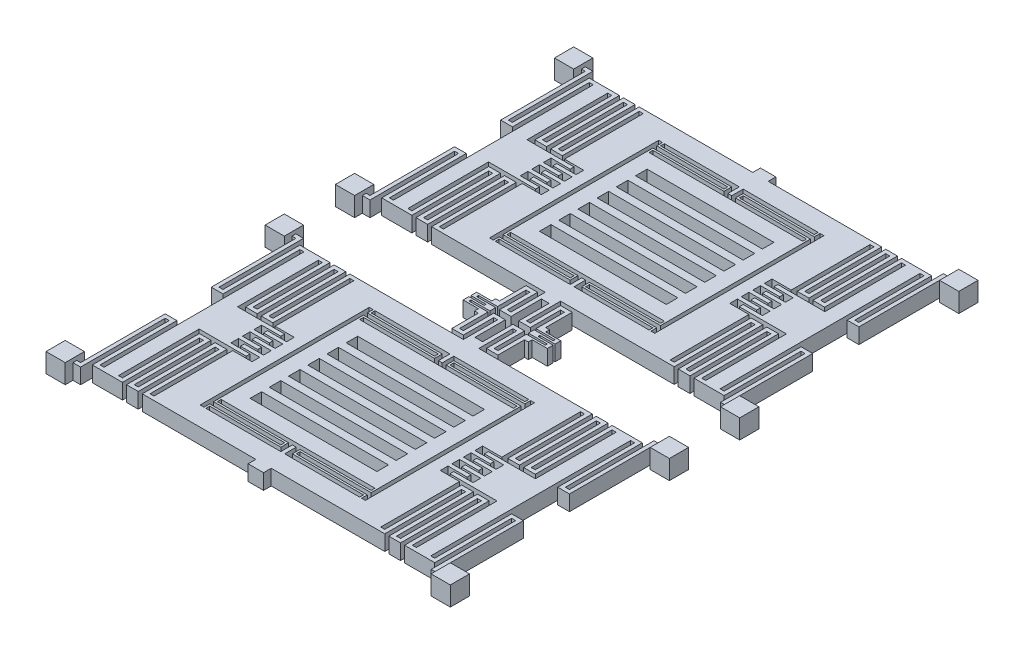
SolidWorks part; units mm, degrees
ref_plane "Front Plane" through (0, 0, 0) normal (0, 0, 1) x (1, 0, 0)
ref_plane "Top Plane" through (0, 0, 0) normal (0, 1, 0) x (1, 0, 0)
ref_plane "Right Plane" through (0, 0, 0) normal (1, 0, 0) x (0, 0, -1)
sketch "Sketch1" plane through (0, 0, 0) normal (0, 1, 0) x (1, 0, 0)
  line L0 (-0.165, 0.06) -> (-0.165, 0.09)
  line L1 (-0.205, -0.18) -> (0.205, -0.18)
  line L2 (-0.205, -0.18) -> (-0.205, 0.18)
  line L3 (-0.205, 0.18) -> (0.205, 0.18)
  line L4 (0.205, -0.18) -> (0.205, 0.18)
  line L5 (0, 0.18) -> (0, -0.18) construction
  line L6 (-0.205, 0) -> (0.205, 0) construction
  line L7 (0.165, 0.01) -> (-0.165, 0.01)
  line L8 (0.165, 0.01) -> (0.165, 0.04)
  line L9 (0.165, 0.04) -> (-0.165, 0.04)
  line L10 (-0.165, 0.01) -> (-0.165, 0.04)
  line L11 (0, 0.04) -> (0, 0.01) construction
  line L12 (0.165, 0.025) -> (-0.165, 0.025) construction
  line L13 (0.165, 0.09) -> (-0.165, 0.09)
  line L14 (0.165, 0.06) -> (-0.165, 0.06)
  line L15 (0.165, 0.06) -> (0.165, 0.09)
  line L16 (-0.165, 0.11) -> (-0.165, 0.14)
  line L17 (0.165, 0.14) -> (-0.165, 0.14)
  line L18 (0.165, 0.11) -> (-0.165, 0.11)
  line L19 (0.165, 0.11) -> (0.165, 0.14)
  line L20 (-0.165, 0.01) -> (-0.165, 0.06) construction
  line L21 (0.165, -0.11) -> (-0.165, -0.11)
  line L22 (0.165, -0.11) -> (0.165, -0.14)
  line L23 (0.165, -0.14) -> (-0.165, -0.14)
  line L24 (-0.165, -0.11) -> (-0.165, -0.14)
  line L25 (0.165, -0.06) -> (-0.165, -0.06)
  line L26 (0.165, -0.06) -> (0.165, -0.09)
  line L27 (0.165, -0.09) -> (-0.165, -0.09)
  line L28 (-0.165, -0.06) -> (-0.165, -0.09)
  line L29 (0.165, -0.04) -> (-0.165, -0.04)
  line L30 (-0.165, -0.01) -> (-0.165, -0.04)
  line L31 (0.165, -0.01) -> (-0.165, -0.01)
  line L32 (0.165, -0.01) -> (0.165, -0.04)
  point P0 (0, 0)
  point P4 (0, 0.025)
  dimension "D1" = 0.36
  dimension "D2" = 0.41
  dimension "D3" = 0.33
  dimension "D4" = 0.03
  dimension "D5" = 0.01
  dimension "D7" = 0.05
  dimension "D6" = 3
extrude "Boss-Extrude1" add sketch "Sketch1" along normal blind 0.04
sketch "Sketch2" plane through (0, 0, 0) normal (0, 1, 0) x (1, 0, 0)
  line L0 (0.2254, 0) -> (-0.371, 0) construction
  line L5 (0, 0) -> (0, 0.338) construction
  line L7 (-0.215, -0.22) -> (-0.215, 0.22)
  line L13 (-0.295, 0.27) -> (-0.02, 0.27)
  line L15 (-0.005, 0.22) -> (-0.2, 0.22)
  line L16 (-0.205, 0.18) -> (-0.205, -0.18) construction
  line L18 (0.005, 0.19) -> (-0.005, 0.19)
  line L19 (-0.005, 0.19) -> (-0.005, 0.22)
  line L20 (-0.205, 0.18) -> (-0.205, 0.195)
  line L21 (-0.205, 0.195) -> (-0.02, 0.195)
  line L22 (-0.02, 0.195) -> (-0.02, 0.205)
  line L23 (-0.02, 0.205) -> (-0.205, 0.205)
  line L24 (-0.205, 0.205) -> (-0.205, 0.22)
  line L26 (-0.2, 0.22) -> (-0.2, 0.21)
  line L27 (-0.2, 0.21) -> (-0.015, 0.21)
  line L28 (-0.015, 0.21) -> (-0.015, 0.19)
  line L29 (-0.015, 0.19) -> (-0.2, 0.19)
  line L30 (-0.2, 0.19) -> (-0.2, 0.18)
  line L31 (0.205, 0.18) -> (-0.205, 0.18) construction
  line L32 (-0.2, 0.18) -> (-0.205, 0.18)
  line L33 (-0.205, 0.22) -> (-0.215, 0.22)
  line L34 (-0.295, -0.005) -> (-0.295, 0.005)
  line L35 (-0.295, 0.005) -> (-0.245, 0.005)
  line L36 (-0.245, 0.005) -> (-0.245, 0.025)
  line L37 (-0.245, 0.055) -> (-0.295, 0.055)
  line L38 (-0.295, 0.055) -> (-0.295, 0.27)
  line L39 (-0.245, 0.035) -> (-0.295, 0.035)
  line L40 (-0.295, 0.035) -> (-0.295, 0.025)
  line L41 (-0.295, 0.025) -> (-0.245, 0.025)
  line L42 (-0.245, 0.035) -> (-0.245, 0.055)
  line L43 (0.295, -0.005) -> (0.295, 0.005)
  line L45 (0.215, -0.22) -> (0.215, 0.22)
  line L46 (0.205, 0.22) -> (0.215, 0.22)
  line L47 (0.205, 0.205) -> (0.205, 0.22)
  line L48 (0.02, 0.205) -> (0.205, 0.205)
  line L49 (0.02, 0.195) -> (0.02, 0.205)
  line L50 (0.205, 0.195) -> (0.02, 0.195)
  line L51 (0.205, 0.18) -> (0.205, 0.195)
  line L52 (0.2, 0.18) -> (0.205, 0.18)
  line L53 (0.2, 0.19) -> (0.2, 0.18)
  line L54 (0.015, 0.19) -> (0.2, 0.19)
  line L55 (0.015, 0.21) -> (0.015, 0.19)
  line L56 (0.2, 0.21) -> (0.015, 0.21)
  line L57 (0.2, 0.22) -> (0.2, 0.21)
  line L58 (0.005, 0.22) -> (0.2, 0.22)
  line L59 (0.005, 0.19) -> (0.005, 0.22)
  line L60 (0.295, 0.055) -> (0.295, 0.27)
  line L61 (0.245, 0.055) -> (0.295, 0.055)
  line L62 (0.245, 0.035) -> (0.245, 0.055)
  line L63 (0.245, 0.035) -> (0.295, 0.035)
  line L64 (0.295, 0.035) -> (0.295, 0.025)
  line L65 (0.295, 0.025) -> (0.245, 0.025)
  line L66 (0.245, 0.005) -> (0.245, 0.025)
  line L67 (0.295, 0.005) -> (0.245, 0.005)
  line L68 (0.205, -0.22) -> (0.215, -0.22)
  line L69 (0.205, -0.205) -> (0.205, -0.22)
  line L70 (0.02, -0.205) -> (0.205, -0.205)
  line L71 (0.02, -0.195) -> (0.02, -0.205)
  line L72 (0.205, -0.195) -> (0.02, -0.195)
  line L73 (0.205, -0.18) -> (0.205, -0.195)
  line L74 (0.2, -0.18) -> (0.205, -0.18)
  line L75 (0.2, -0.19) -> (0.2, -0.18)
  line L76 (0.015, -0.19) -> (0.2, -0.19)
  line L77 (0.015, -0.21) -> (0.015, -0.19)
  line L78 (0.2, -0.21) -> (0.015, -0.21)
  line L79 (0.2, -0.22) -> (0.2, -0.21)
  line L80 (0.005, -0.22) -> (0.2, -0.22)
  line L81 (0.005, -0.19) -> (0.005, -0.22)
  line L82 (0.005, -0.19) -> (-0.005, -0.19)
  line L83 (-0.005, -0.19) -> (-0.005, -0.22)
  line L84 (-0.005, -0.22) -> (-0.2, -0.22)
  line L85 (-0.2, -0.22) -> (-0.2, -0.21)
  line L86 (-0.2, -0.21) -> (-0.015, -0.21)
  line L87 (-0.015, -0.21) -> (-0.015, -0.19)
  line L88 (-0.015, -0.19) -> (-0.2, -0.19)
  line L89 (-0.2, -0.19) -> (-0.2, -0.18)
  line L90 (-0.2, -0.18) -> (-0.205, -0.18)
  line L91 (-0.205, -0.18) -> (-0.205, -0.195)
  line L92 (-0.205, -0.195) -> (-0.02, -0.195)
  line L93 (-0.02, -0.195) -> (-0.02, -0.205)
  line L94 (-0.02, -0.205) -> (-0.205, -0.205)
  line L95 (-0.205, -0.205) -> (-0.205, -0.22)
  line L96 (-0.205, -0.22) -> (-0.215, -0.22)
  line L97 (-0.295, -0.005) -> (-0.245, -0.005)
  line L98 (-0.245, -0.005) -> (-0.245, -0.025)
  line L99 (-0.295, -0.025) -> (-0.245, -0.025)
  line L100 (-0.295, -0.035) -> (-0.295, -0.025)
  line L101 (-0.245, -0.035) -> (-0.295, -0.035)
  line L102 (-0.245, -0.035) -> (-0.245, -0.055)
  line L103 (-0.245, -0.055) -> (-0.295, -0.055)
  line L104 (-0.295, -0.055) -> (-0.295, -0.27)
  line L105 (-0.295, -0.27) -> (-0.02, -0.27)
  line L106 (0.295, -0.055) -> (0.295, -0.27)
  line L107 (0.245, -0.055) -> (0.295, -0.055)
  line L108 (0.245, -0.035) -> (0.245, -0.055)
  line L109 (0.245, -0.035) -> (0.295, -0.035)
  line L110 (0.295, -0.035) -> (0.295, -0.025)
  line L111 (0.295, -0.025) -> (0.245, -0.025)
  line L112 (0.245, -0.005) -> (0.245, -0.025)
  line L113 (0.295, -0.005) -> (0.245, -0.005)
  line L114 (0.02, 0.27) -> (0.295, 0.27)
  line L116 (-0.02, 0.27) -> (-0.02, 0.29)
  line L117 (-0.02, 0.29) -> (0.02, 0.29)
  line L118 (0.02, 0.27) -> (0.02, 0.29)
  line L119 (0, 0.29) -> (0, 0.27) construction
  line L120 (-0.02, 0.28) -> (0.02, 0.28) construction
  line L121 (0.02, -0.27) -> (0.02, -0.29)
  line L122 (-0.02, -0.29) -> (0.02, -0.29)
  line L123 (-0.02, -0.27) -> (-0.02, -0.29)
  line L124 (0.02, -0.27) -> (0.295, -0.27)
  point P2 (-0.21, -0.22)
  point P759 (0, 0.28)
  dimension "D2" = 0.01
  dimension "D3" = 0.01
  dimension "D4" = 0.54
  dimension "D5" = 0.03
  dimension "D6" = 0.59
  dimension "D7" = 0.015
  dimension "D8" = 0.005
  dimension "D10" = 0.01
  dimension "D11" = 0.02
  dimension "D12" = 0.185
  dimension "D13" = 0.005
  dimension "D14" = 0.005
  dimension "D15" = 0.005
  dimension "D16" = 0.05
  dimension "D17" = 0.11
  dimension "D18" = 0.01
  dimension "D19" = 0.44
  dimension "D20" = 0.04
extrude "Boss-Extrude2" add sketch "Sketch2" along normal blind 0.04
sketch "Sketch3" plane through (0, 0, 0) normal (0, 1, 0) x (1, 0, 0)
  line L1 (-0.315, 0.01) -> (-0.265, 0.01)
  line L2 (-0.265, 0.01) -> (-0.265, 0.02)
  line L3 (-0.265, 0.02) -> (-0.315, 0.02)
  line L4 (-0.315, 0.02) -> (-0.315, 0.04)
  line L5 (-0.315, 0.04) -> (-0.265, 0.04)
  line L6 (-0.265, 0.04) -> (-0.265, 0.05)
  line L7 (-0.265, 0.05) -> (-0.315, 0.05)
  line L8 (-0.315, 0.05) -> (-0.3875, 0.05)
  line L11 (0, 0) -> (-0.4867, 0) construction
  line L12 (-0.295, 0.035) -> (-0.295, 0.025) construction
  line L14 (0, 0) -> (0, 0.4313) construction
  line L20 (-0.3875, 0.27) -> (-0.367, 0.27)
  line L21 (-0.367, 0.27) -> (-0.367, 0.07)
  line L22 (-0.367, 0.07) -> (-0.3565, 0.07)
  line L23 (-0.3565, 0.07) -> (-0.3565, 0.27)
  line L24 (-0.3565, 0.27) -> (-0.326, 0.27)
  line L25 (-0.326, 0.27) -> (-0.326, 0.07)
  line L26 (-0.326, 0.07) -> (-0.3155, 0.07)
  line L27 (-0.3155, 0.07) -> (-0.3155, 0.27)
  line L28 (-0.3155, 0.27) -> (-0.295, 0.27)
  line L30 (-0.3875, 0.26) -> (-0.377, 0.26)
  line L31 (-0.377, 0.26) -> (-0.377, 0.06)
  line L32 (-0.377, 0.06) -> (-0.3465, 0.06)
  line L33 (-0.3465, 0.06) -> (-0.3465, 0.26)
  line L34 (-0.3465, 0.26) -> (-0.336, 0.26)
  line L35 (-0.336, 0.26) -> (-0.336, 0.06)
  line L36 (-0.336, 0.06) -> (-0.3055, 0.06)
  line L37 (-0.3055, 0.06) -> (-0.3055, 0.26)
  line L38 (-0.3055, 0.26) -> (-0.295, 0.26)
  line L39 (-0.295, 0.27) -> (-0.295, 0.055) construction
  line L40 (-0.295, 0.27) -> (-0.295, 0.26)
  line L41 (-0.3875, 0.26) -> (-0.3875, 0.05)
  line L136 (-0.425, 0.05) -> (-0.425, -0.05)
  line L138 (-0.315, -0.01) -> (-0.315, 0.01)
  line L139 (-0.3875, 0.27) -> (-0.425, 0.27)
  line L140 (-0.425, 0.05) -> (-0.425, 0.26)
  line L141 (-0.4063, 0.27) -> (-0.4063, -0.0104) construction
  line L142 (-0.456, 0.27) -> (-0.456, 0.29)
  line L143 (-0.456, 0.29) -> (-0.476, 0.29)
  line L144 (-0.476, 0.29) -> (-0.476, 0.28)
  line L145 (-0.476, 0.28) -> (-0.466, 0.28)
  line L146 (-0.466, 0.28) -> (-0.466, 0.26)
  line L147 (-0.425, -0.05) -> (-0.425, -0.26)
  line L148 (-0.425, -0.26) -> (-0.4355, -0.26)
  line L149 (-0.4355, -0.26) -> (-0.4355, -0.06)
  line L150 (-0.4355, -0.06) -> (-0.466, -0.06)
  line L151 (-0.466, -0.06) -> (-0.466, -0.26)
  line L152 (-0.456, 0.07) -> (-0.456, 0.27)
  line L153 (-0.466, 0.06) -> (-0.466, 0.26)
  line L154 (-0.4455, 0.07) -> (-0.456, 0.07)
  line L155 (-0.4355, 0.06) -> (-0.466, 0.06)
  line L156 (-0.4455, 0.27) -> (-0.4455, 0.07)
  line L157 (-0.4355, 0.26) -> (-0.4355, 0.06)
  line L158 (-0.425, 0.27) -> (-0.4455, 0.27)
  line L159 (-0.425, 0.26) -> (-0.4355, 0.26)
  line L160 (-0.466, -0.28) -> (-0.466, -0.26)
  line L161 (-0.476, -0.28) -> (-0.466, -0.28)
  line L162 (-0.476, -0.29) -> (-0.476, -0.28)
  line L163 (-0.456, -0.29) -> (-0.476, -0.29)
  line L164 (-0.456, -0.27) -> (-0.456, -0.29)
  line L165 (-0.456, -0.07) -> (-0.456, -0.27)
  line L166 (-0.4455, -0.07) -> (-0.456, -0.07)
  line L167 (-0.4455, -0.27) -> (-0.4455, -0.07)
  line L168 (-0.425, -0.27) -> (-0.4455, -0.27)
  line L169 (-0.3875, -0.27) -> (-0.425, -0.27)
  line L170 (-0.3875, -0.27) -> (-0.367, -0.27)
  line L171 (-0.367, -0.27) -> (-0.367, -0.07)
  line L172 (-0.367, -0.07) -> (-0.3565, -0.07)
  line L173 (-0.3565, -0.07) -> (-0.3565, -0.27)
  line L174 (-0.3565, -0.27) -> (-0.326, -0.27)
  line L175 (-0.326, -0.27) -> (-0.326, -0.07)
  line L176 (-0.326, -0.07) -> (-0.3155, -0.07)
  line L177 (-0.3155, -0.07) -> (-0.3155, -0.27)
  line L178 (-0.3155, -0.27) -> (-0.295, -0.27)
  line L179 (-0.295, -0.27) -> (-0.295, -0.26)
  line L180 (-0.3055, -0.26) -> (-0.295, -0.26)
  line L181 (-0.3055, -0.06) -> (-0.3055, -0.26)
  line L182 (-0.336, -0.06) -> (-0.3055, -0.06)
  line L183 (-0.336, -0.26) -> (-0.336, -0.06)
  line L184 (-0.3465, -0.26) -> (-0.336, -0.26)
  line L185 (-0.3465, -0.06) -> (-0.3465, -0.26)
  line L186 (-0.377, -0.06) -> (-0.3465, -0.06)
  line L187 (-0.377, -0.26) -> (-0.377, -0.06)
  line L188 (-0.3875, -0.26) -> (-0.377, -0.26)
  line L189 (-0.3875, -0.26) -> (-0.3875, -0.05)
  line L190 (-0.315, -0.05) -> (-0.3875, -0.05)
  line L191 (-0.265, -0.05) -> (-0.315, -0.05)
  line L192 (-0.265, -0.04) -> (-0.265, -0.05)
  line L193 (-0.315, -0.04) -> (-0.265, -0.04)
  line L194 (-0.315, -0.02) -> (-0.315, -0.04)
  line L195 (-0.265, -0.02) -> (-0.315, -0.02)
  line L196 (-0.265, -0.01) -> (-0.265, -0.02)
  line L197 (-0.315, -0.01) -> (-0.265, -0.01)
  line L198 (0.425, 0.05) -> (0.425, -0.05)
  line L199 (0.425, 0.05) -> (0.425, 0.26)
  line L200 (0.425, 0.26) -> (0.4355, 0.26)
  line L201 (0.4355, 0.26) -> (0.4355, 0.06)
  line L202 (0.4355, 0.06) -> (0.466, 0.06)
  line L203 (0.466, 0.06) -> (0.466, 0.26)
  line L204 (0.466, 0.28) -> (0.466, 0.26)
  line L205 (0.476, 0.28) -> (0.466, 0.28)
  line L206 (0.476, 0.29) -> (0.476, 0.28)
  line L207 (0.456, 0.29) -> (0.476, 0.29)
  line L208 (0.456, 0.27) -> (0.456, 0.29)
  line L209 (0.456, 0.07) -> (0.456, 0.27)
  line L210 (0.4455, 0.07) -> (0.456, 0.07)
  line L211 (0.4455, 0.27) -> (0.4455, 0.07)
  line L212 (0.425, 0.27) -> (0.4455, 0.27)
  line L213 (0.3875, 0.27) -> (0.425, 0.27)
  line L214 (0.3875, 0.27) -> (0.367, 0.27)
  line L215 (0.367, 0.27) -> (0.367, 0.07)
  line L216 (0.367, 0.07) -> (0.3565, 0.07)
  line L217 (0.3565, 0.07) -> (0.3565, 0.27)
  line L218 (0.3565, 0.27) -> (0.326, 0.27)
  line L219 (0.326, 0.27) -> (0.326, 0.07)
  line L220 (0.326, 0.07) -> (0.3155, 0.07)
  line L221 (0.3155, 0.07) -> (0.3155, 0.27)
  line L222 (0.3155, 0.27) -> (0.295, 0.27)
  line L223 (0.295, 0.27) -> (0.295, 0.26)
  line L224 (0.3055, 0.26) -> (0.295, 0.26)
  line L225 (0.3055, 0.06) -> (0.3055, 0.26)
  line L226 (0.336, 0.06) -> (0.3055, 0.06)
  line L227 (0.336, 0.26) -> (0.336, 0.06)
  line L228 (0.3465, 0.26) -> (0.336, 0.26)
  line L229 (0.3465, 0.06) -> (0.3465, 0.26)
  line L230 (0.377, 0.06) -> (0.3465, 0.06)
  line L231 (0.377, 0.26) -> (0.377, 0.06)
  line L232 (0.3875, 0.26) -> (0.377, 0.26)
  line L233 (0.3875, 0.26) -> (0.3875, 0.05)
  line L234 (0.315, 0.05) -> (0.3875, 0.05)
  line L235 (0.265, 0.05) -> (0.315, 0.05)
  line L236 (0.265, 0.04) -> (0.265, 0.05)
  line L237 (0.315, 0.04) -> (0.265, 0.04)
  line L238 (0.315, 0.02) -> (0.315, 0.04)
  line L239 (0.265, 0.02) -> (0.315, 0.02)
  line L240 (0.265, 0.01) -> (0.265, 0.02)
  line L241 (0.315, 0.01) -> (0.265, 0.01)
  line L242 (0.315, -0.01) -> (0.315, 0.01)
  line L243 (0.315, -0.01) -> (0.265, -0.01)
  line L244 (0.265, -0.01) -> (0.265, -0.02)
  line L245 (0.265, -0.02) -> (0.315, -0.02)
  line L246 (0.315, -0.02) -> (0.315, -0.04)
  line L247 (0.315, -0.04) -> (0.265, -0.04)
  line L248 (0.265, -0.04) -> (0.265, -0.05)
  line L249 (0.265, -0.05) -> (0.315, -0.05)
  line L250 (0.315, -0.05) -> (0.3875, -0.05)
  line L251 (0.3875, -0.26) -> (0.3875, -0.05)
  line L252 (0.3875, -0.26) -> (0.377, -0.26)
  line L253 (0.377, -0.26) -> (0.377, -0.06)
  line L254 (0.377, -0.06) -> (0.3465, -0.06)
  line L255 (0.3465, -0.06) -> (0.3465, -0.26)
  line L256 (0.3465, -0.26) -> (0.336, -0.26)
  line L257 (0.336, -0.26) -> (0.336, -0.06)
  line L258 (0.336, -0.06) -> (0.3055, -0.06)
  line L259 (0.3055, -0.06) -> (0.3055, -0.26)
  line L260 (0.3055, -0.26) -> (0.295, -0.26)
  line L261 (0.295, -0.27) -> (0.295, -0.26)
  line L262 (0.3155, -0.27) -> (0.295, -0.27)
  line L263 (0.3155, -0.07) -> (0.3155, -0.27)
  line L264 (0.326, -0.07) -> (0.3155, -0.07)
  line L265 (0.326, -0.27) -> (0.326, -0.07)
  line L266 (0.3565, -0.27) -> (0.326, -0.27)
  line L267 (0.3565, -0.07) -> (0.3565, -0.27)
  line L268 (0.367, -0.07) -> (0.3565, -0.07)
  line L269 (0.367, -0.27) -> (0.367, -0.07)
  line L270 (0.3875, -0.27) -> (0.367, -0.27)
  line L271 (0.3875, -0.27) -> (0.425, -0.27)
  line L272 (0.425, -0.27) -> (0.4455, -0.27)
  line L273 (0.4455, -0.27) -> (0.4455, -0.07)
  line L274 (0.4455, -0.07) -> (0.456, -0.07)
  line L275 (0.456, -0.07) -> (0.456, -0.27)
  line L276 (0.456, -0.27) -> (0.456, -0.29)
  line L277 (0.456, -0.29) -> (0.476, -0.29)
  line L278 (0.476, -0.29) -> (0.476, -0.28)
  line L279 (0.476, -0.28) -> (0.466, -0.28)
  line L280 (0.466, -0.28) -> (0.466, -0.26)
  line L281 (0.466, -0.06) -> (0.466, -0.26)
  line L282 (0.4355, -0.06) -> (0.466, -0.06)
  line L283 (0.4355, -0.26) -> (0.4355, -0.06)
  line L284 (0.425, -0.26) -> (0.4355, -0.26)
  line L285 (0.425, -0.05) -> (0.425, -0.26)
  point P15 (-0.3823, 0.26)
  point P21 (-0.315, 0.03)
  point P25 (-0.466, 0.27)
  dimension "D2" = 0.11
  dimension "D3" = 0.02
  dimension "D4" = 0.181
  dimension "D5" = 0.02
  dimension "D6" = 0.02
  dimension "D7" = 0.1
  dimension "D8" = 0.05
  dimension "D9" = 0.0375
  dimension "D10" = 0.01
  dimension "D12" = 0.01
  dimension "D13" = 0.01
  dimension "D14" = 0.01
  dimension "D15" = 0.01
extrude "Boss-Extrude3" add sketch "Sketch3" along normal blind 0.04
sketch "Sketch4" plane through (0, 0, 0) normal (0, 1, 0) x (1, 0, 0)
  line L0 (-0.476, -0.28) -> (-0.476, -0.29) construction
  line L1 (-0.476, -0.26) -> (-0.526, -0.26)
  line L2 (-0.476, -0.26) -> (-0.476, -0.31)
  line L3 (-0.476, -0.31) -> (-0.526, -0.31)
  line L4 (-0.526, -0.26) -> (-0.526, -0.31)
  line L5 (-0.501, -0.31) -> (-0.501, -0.26) construction
  line L6 (-0.476, -0.285) -> (-0.526, -0.285) construction
  line L7 (0, 0) -> (-0.6389, 0) construction
  line L8 (0, 0) -> (0, -0.3331) construction
  line L9 (-0.476, 0.31) -> (-0.526, 0.31)
  line L10 (-0.526, 0.26) -> (-0.526, 0.31)
  line L11 (-0.476, 0.26) -> (-0.526, 0.26)
  line L12 (-0.476, 0.26) -> (-0.476, 0.31)
  line L13 (0.476, -0.31) -> (0.526, -0.31)
  line L14 (0.526, -0.26) -> (0.526, -0.31)
  line L15 (0.476, -0.26) -> (0.526, -0.26)
  line L16 (0.476, -0.26) -> (0.476, -0.31)
  line L17 (0.476, 0.26) -> (0.476, 0.31)
  line L18 (0.476, 0.26) -> (0.526, 0.26)
  line L19 (0.526, 0.26) -> (0.526, 0.31)
  line L20 (0.476, 0.31) -> (0.526, 0.31)
  point P760 (-0.501, -0.285)
  dimension "D1" = 0.05
  dimension "D2" = 0.05
extrude "Boss-Extrude4" add sketch "Sketch4" along normal blind 0.05
sketch "Sketch5" plane through (0, 0, 0) normal (0, 1, 0) x (1, 0, 0)
  line L8 (-0.06, -0.28) -> (-0.06, -0.349)
  line L22 (-0.02, -0.29) -> (-0.02, -0.359)
  line L42 (-0.02, -0.359) -> (-0.03, -0.359)
  line L83 (-0.03, -0.359) -> (-0.03, -0.28)
  line L84 (-0.03, -0.28) -> (-0.06, -0.28)
  line L85 (-0.06, -0.349) -> (-0.07, -0.349)
  line L86 (-0.07, -0.349) -> (-0.07, -0.359)
  line L87 (-0.07, -0.359) -> (-0.1095, -0.359)
  line L88 (-0.1095, -0.359) -> (-0.1095, -0.374)
  line L89 (-0.1095, -0.374) -> (-0.07, -0.374)
  line L90 (-0.07, -0.374) -> (-0.07, -0.379)
  line L91 (-0.02, -0.29) -> (-0.01, -0.29)
  line L92 (-0.02, -0.29) -> (0.02, -0.29) construction
  line L93 (-0.01, -0.29) -> (-0.01, -0.369)
  line L94 (-0.01, -0.369) -> (-0.04, -0.369)
  line L95 (-0.04, -0.369) -> (-0.04, -0.29)
  line L96 (-0.04, -0.29) -> (-0.05, -0.29)
  line L97 (-0.05, -0.29) -> (-0.05, -0.364)
  line L98 (-0.05, -0.364) -> (-0.0995, -0.364)
  line L99 (-0.0995, -0.364) -> (-0.0995, -0.369)
  line L100 (-0.0995, -0.369) -> (-0.05, -0.369)
  line L101 (-0.05, -0.369) -> (-0.05, -0.3765)
  line L102 (-0.1205, -0.3765) -> (0.0783, -0.3765) construction
  line L103 (0, -0.2825) -> (0, -0.4298) construction
  line L104 (-0.05, -0.384) -> (-0.05, -0.3765)
  line L105 (-0.0995, -0.384) -> (-0.05, -0.384)
  line L106 (-0.0995, -0.389) -> (-0.0995, -0.384)
  line L107 (-0.05, -0.389) -> (-0.0995, -0.389)
  line L108 (-0.05, -0.463) -> (-0.05, -0.389)
  line L109 (-0.04, -0.463) -> (-0.05, -0.463)
  line L110 (-0.04, -0.384) -> (-0.04, -0.463)
  line L111 (-0.01, -0.384) -> (-0.04, -0.384)
  line L112 (-0.01, -0.463) -> (-0.01, -0.384)
  line L113 (-0.02, -0.463) -> (-0.01, -0.463)
  line L114 (-0.1095, -0.379) -> (-0.07, -0.379)
  line L115 (-0.1095, -0.394) -> (-0.1095, -0.379)
  line L116 (-0.07, -0.394) -> (-0.1095, -0.394)
  line L117 (-0.07, -0.404) -> (-0.07, -0.394)
  line L118 (-0.06, -0.404) -> (-0.07, -0.404)
  line L119 (-0.03, -0.473) -> (-0.06, -0.473)
  line L120 (-0.03, -0.394) -> (-0.03, -0.473)
  line L121 (-0.02, -0.394) -> (-0.03, -0.394)
  line L122 (-0.02, -0.463) -> (-0.02, -0.394)
  line L123 (-0.06, -0.473) -> (-0.06, -0.404)
  line L124 (0.06, -0.473) -> (0.06, -0.404)
  line L125 (0.02, -0.463) -> (0.02, -0.394)
  line L126 (0.02, -0.394) -> (0.03, -0.394)
  line L127 (0.03, -0.394) -> (0.03, -0.473)
  line L128 (0.03, -0.473) -> (0.06, -0.473)
  line L129 (0.06, -0.404) -> (0.07, -0.404)
  line L130 (0.07, -0.404) -> (0.07, -0.394)
  line L131 (0.07, -0.394) -> (0.1095, -0.394)
  line L132 (0.1095, -0.394) -> (0.1095, -0.379)
  line L133 (0.1095, -0.379) -> (0.07, -0.379)
  line L134 (0.02, -0.463) -> (0.01, -0.463)
  line L135 (0.01, -0.463) -> (0.01, -0.384)
  line L136 (0.01, -0.384) -> (0.04, -0.384)
  line L137 (0.04, -0.384) -> (0.04, -0.463)
  line L138 (0.04, -0.463) -> (0.05, -0.463)
  line L139 (0.05, -0.463) -> (0.05, -0.389)
  line L140 (0.05, -0.389) -> (0.0995, -0.389)
  line L141 (0.0995, -0.389) -> (0.0995, -0.384)
  line L142 (0.0995, -0.384) -> (0.05, -0.384)
  line L143 (0.05, -0.384) -> (0.05, -0.3765)
  line L144 (0.05, -0.369) -> (0.05, -0.3765)
  line L145 (0.0995, -0.369) -> (0.05, -0.369)
  line L146 (0.0995, -0.364) -> (0.0995, -0.369)
  line L147 (0.05, -0.364) -> (0.0995, -0.364)
  line L148 (0.05, -0.29) -> (0.05, -0.364)
  line L149 (0.04, -0.29) -> (0.05, -0.29)
  line L150 (0.04, -0.369) -> (0.04, -0.29)
  line L151 (0.01, -0.369) -> (0.04, -0.369)
  line L152 (0.01, -0.29) -> (0.01, -0.369)
  line L153 (0.02, -0.29) -> (0.01, -0.29)
  line L154 (0.07, -0.374) -> (0.07, -0.379)
  line L155 (0.1095, -0.374) -> (0.07, -0.374)
  line L156 (0.1095, -0.359) -> (0.1095, -0.374)
  line L157 (0.07, -0.359) -> (0.1095, -0.359)
  line L158 (0.07, -0.349) -> (0.07, -0.359)
  line L159 (0.06, -0.349) -> (0.07, -0.349)
  line L160 (0.03, -0.28) -> (0.06, -0.28)
  line L161 (0.03, -0.359) -> (0.03, -0.28)
  line L162 (0.02, -0.359) -> (0.03, -0.359)
  line L163 (0.02, -0.29) -> (0.02, -0.359)
  line L164 (0.06, -0.28) -> (0.06, -0.349)
  point P29 (-0.025, -0.384)
  point P40 (-0.1095, -0.3665)
  point P69 (0.1095, -0.3865)
  dimension "D1" = 0.01
  dimension "D2" = 0.01
  dimension "D3" = 0.005
  dimension "D4" = 0.01
  dimension "D5" = 0.005
  dimension "D6" = 0.01
  dimension "D7" = 0.193
  dimension "D8" = 0.219
  dimension "D9" = 0.01
  dimension "D10" = 0.015
  dimension "D11" = 0.01
  dimension "D12" = 0.01
extrude "Boss-Extrude5" add sketch "Sketch5" along normal blind 0.04
sketch3d "3DSketch1"
  line L4 (-0.05, 0.04, 0.3765) -> (0.05, 0.04, 0.3765)
  line L5 (-0.05, 0.04, 0.384) -> (-0.05, 0.04, 0.369) construction
  line L9 (0.05, 0.04, 0.369) -> (0.05, 0.04, 0.384) construction
  line L10 (0.05, 0.04, 0.3765) -> (0.05, 0, 0.3765)
  line L11 (0.05, 0, 0.369) -> (0.05, 0, 0.384) construction
  line L12 (0.05, 0, 0.3765) -> (-0.05, 0, 0.3765)
  line L13 (-0.05, 0, 0.384) -> (-0.05, 0, 0.369) construction
  line L14 (-0.05, 0, 0.3765) -> (-0.05, 0.04, 0.3765)
ref_plane "Plane1" through (0, 0, 0.3765) normal (0, 0, 1) x (1, 0, 0)
mirror "Mirror1" about plane through (0, 0, 0.3765) normal (0, 0, 1) of "Boss-Extrude4", "Boss-Extrude3", "Boss-Extrude2"
mirror "Mirror2" about plane through (0, 0, 0.3765) normal (0, 0, 1) of "Boss-Extrude1"
